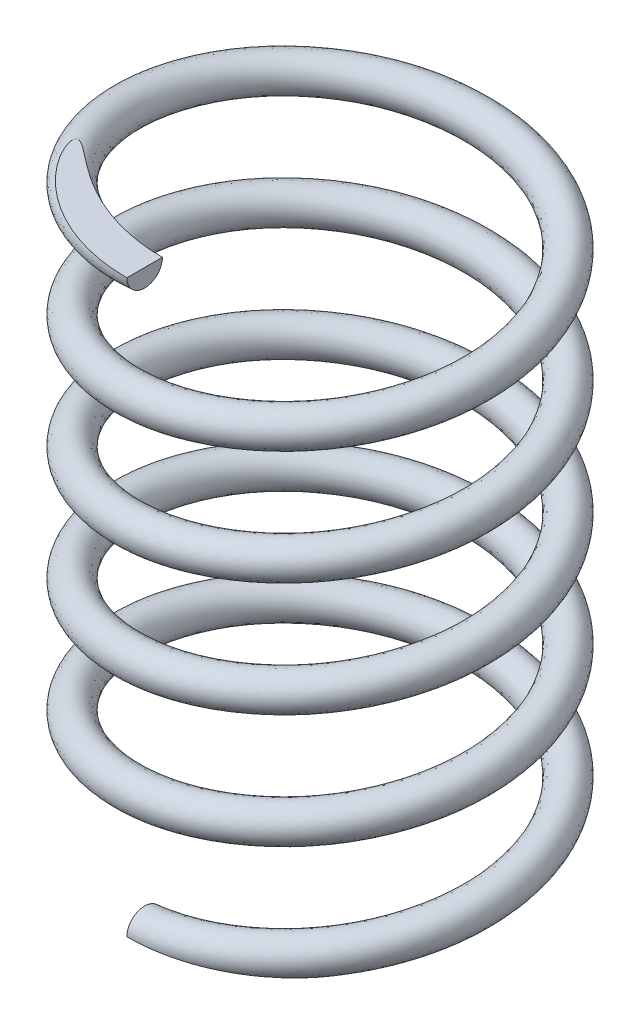
SolidWorks part; units mm, degrees
note: '?' marks a value the reader was unsure of.
material "Простая углеродистая сталь"
ref_plane "Спереди" through (0, 0, 0) normal (0, 0, 1) x (1, 0, 0)
ref_plane "Сверху" through (0, 0, 0) normal (0, 1, 0) x (1, 0, 0)
ref_plane "Справа" through (0, 0, 0) normal (1, 0, 0) x (0, 0, -1)
sketch "Эскиз1" plane through (0, 0, 0) normal (0, 1, 0) x (1, 0, 0)
  circle A0 centre (0, 0) radius 4.4
  dimension "D1" = 8.8
curve "Спираль1" pitch 2.6 height 13 radius 4.4 centre (0, 0, 0) axis (0, 1, 0) start towards (0, 0, 1)
sketch "Эскиз2" plane through (0, 0, 0) normal (1, 0, 0) x (0, 0, -1)
  circle A0 centre (-3.995, 0) radius 0.405
  point P2 (-4.4, 0)
  dimension "D1" = 0.81
sweep "По траектории1" add profiles "Эскиз2" path "Спираль1"
other "Сечение1"
ref_plane "Плоскость1" through (0, 13, 0) normal (0, 1, 0) x (1, 0, 0)
other "Сечение2" flip cut yes
sketch "Эскиз3" plane through (0, 0, 0) normal (0, 0, 1) x (1, 0, 0)
  line L0 (0, 0) -> (0, 16.6067)
ref_axis "Ось1" through (0, 0, 0) along (0, 1, 0)?
